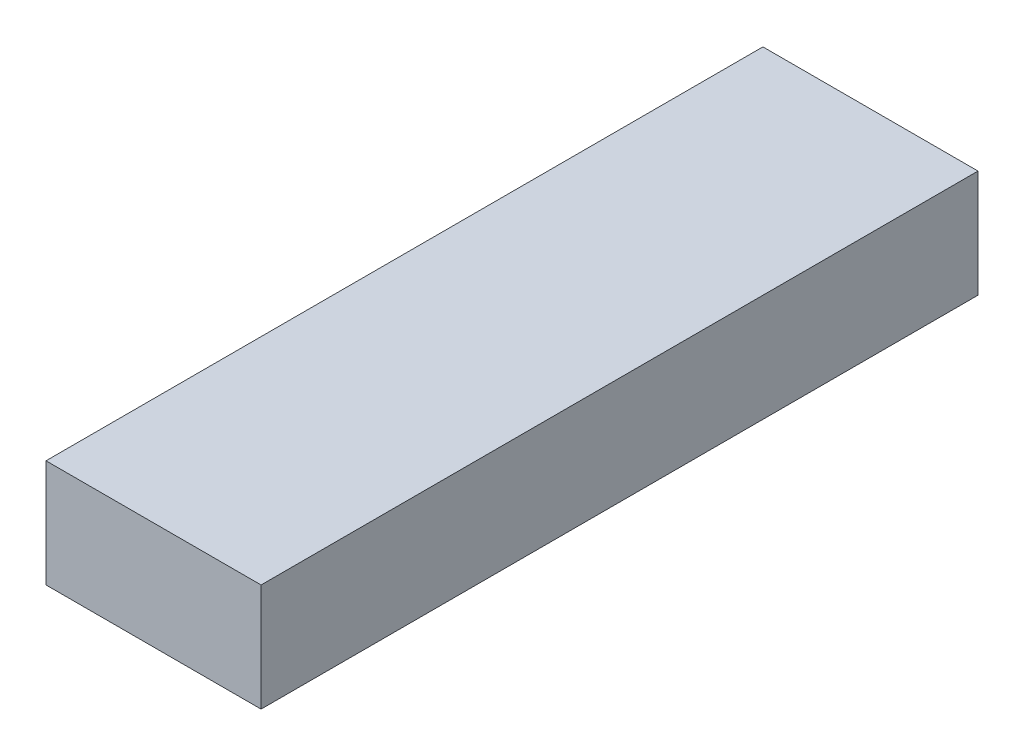
SolidWorks part; units mm, degrees
ref_plane "정면" through (0, 0, 0) normal (0, 0, 1) x (1, 0, 0)
ref_plane "윗면" through (0, 0, 0) normal (0, 1, 0) x (1, 0, 0)
ref_plane "우측면" through (0, 0, 0) normal (1, 0, 0) x (0, 0, -1)
ref_axis "기준축2" through (0, 0, 210) along (0, 0, -1)
ref_axis "기준축4" through (0, 55, 0) along (0, -1, 0)
sketch "스케치1" plane through (0, 0, 0) normal (0, 0, 1) x (1, 0, 0)
  line L1 (-30, 15) -> (30, 15)
  line L2 (-30, 15) -> (-30, -15)
  line L3 (-30, -15) -> (30, -15)
  line L4 (30, 15) -> (30, -15)
  point P5 (0, 15)
  point P7 (30, 0)
  dimension "D1" = 60
  dimension "D2" = 30
extrude "보스-돌출1" add sketch "스케치1" along normal blind 200
